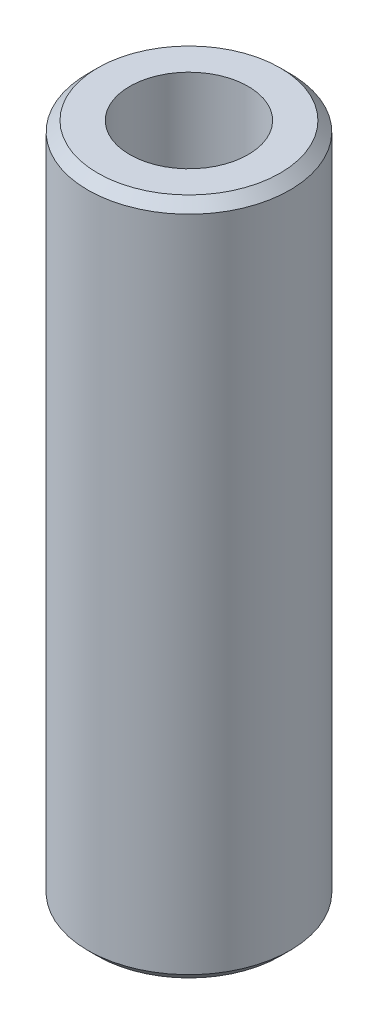
SolidWorks part; units mm, degrees
ref_plane "Front Plane" through (0, 0, 0) normal (0, 0, 1) x (1, 0, 0)
ref_plane "Top Plane" through (0, 0, 0) normal (0, 1, 0) x (1, 0, 0)
ref_plane "Right Plane" through (0, 0, 0) normal (1, 0, 0) x (0, 0, -1)
sketch "Sketch1" plane through (0, 0, 0) normal (0, 1, 0) x (1, 0, 0)
  circle A0 centre (0, 0) radius 22.5
  dimension "SHAFT_OD" = 45
extrude "Boss-Extrude1" add sketch "Sketch1" along normal blind 151.0499
sketch "Sketch2" plane through (0, 0, 0) normal (0, 1, 0) x (1, 0, 0)
  circle A0 centre (0, 0) radius 13.1851
  dimension "BORE_D" = 26.3702
extrude "Cut-Extrude1" cut sketch "Sketch2" along normal through all
chamfer "Chamfer1" distance 2.1798 angle 45 2 edges at (0, 151.0499, 22.5) (0, 0, 22.5)
